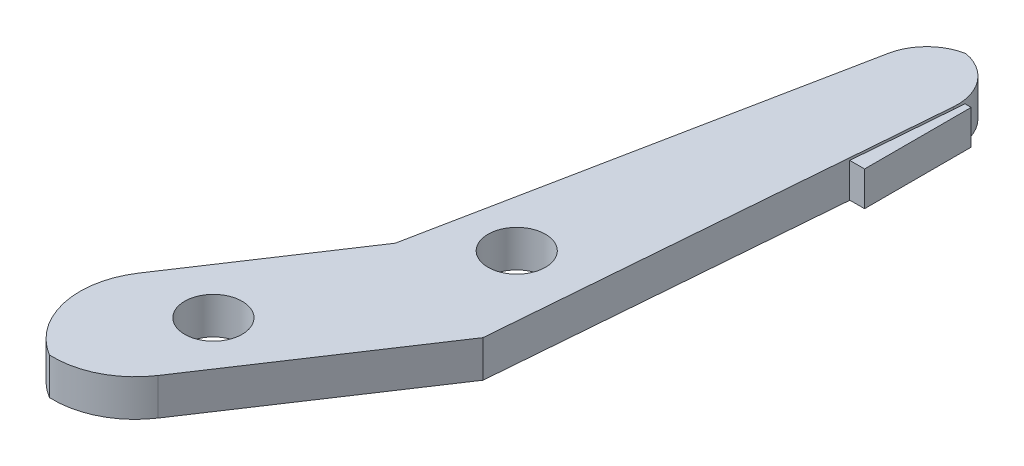
SolidWorks part; units mm, degrees
ref_plane "Front Plane" through (0, 0, 0) normal (0, 0, 1) x (1, 0, 0)
ref_plane "Top Plane" through (0, 0, 0) normal (0, 1, 0) x (1, 0, 0)
ref_plane "Right Plane" through (0, 0, 0) normal (1, 0, 0) x (0, 0, -1)
sketch "Sketch1" plane through (0, 0, 0) normal (0, 1, 0) x (1, 0, 0)
  line L0 (0, 0) -> (9.9579, 14.9947)
  line L1 (9.9579, 14.9947) -> (15.4442, 42.4519)
  line L6 (17.6176, 12.6862) -> (7.6597, -2.3085)
  line L7 (7.6597, -2.3085) -> (0, 0)
  line L9 (17.6176, 12.6862) -> (20.0339, 42.4519)
  line L10 (20.0339, 42.4519) -> (15.4442, 42.4519)
  point P2 (6.3021, 16.8607)
  point P6 (11.5877, 41.7741)
  point P7 (14.3875, 41.5565)
  point P10 (19.5325, 12.1091)
  point P11 (20.0339, 42.4519)
  dimension "D1" = 8
  dimension "D2" = 18
  dimension "D3" = 18
  dimension "D4" = 28
extrude "Boss-Extrude1" add sketch "Sketch1" along normal blind 2.25
fillet "Fillet1" radius 5 2 edges at (7.6597, 1.125, 2.3085) (0, 1.125, 0)
fillet "Fillet2" radius 3 2 edges at (15.4442, 1.125, -42.4519) (20.0339, 1.125, -42.4519)
sketch "Sketch2" plane through (0, 2.25, 0) normal (0, 1, 0) x (1, 0, 0)
  line L0 (17.6176, 12.6862) -> (19.7707, 39.2092) construction
  line L1 (9.7134, 0.7839) -> (17.6176, 12.6862) construction
  circle A0 centre (8.3533, 5.5145) radius 1.75
  circle A1 centre (14.06, 18.2987) radius 1.75
  point P4 (0, 0)
  point P5 (0, 0)
  dimension "D1" = 3.5
  dimension "D2" = 3.5
  dimension "D3" = 14
  dimension "D4" = 4
  dimension "D5" = 3.75
extrude "Cut-Extrude1" cut sketch "Sketch2" against normal through all
ref_plane "Plane1" through (20.2, 0, 0) normal (1, 0, 0) x (0, 0, -1)
sketch "Sketch4" plane through (20.2, -1.4847, -8.2019) normal (1, 0, 0) x (0, 0, -1)
  line L1 (31.6585, 3.5919) -> (25.1585, 3.5919)
  line L2 (31.6585, 3.5919) -> (31.6585, 1.4919)
  line L3 (31.6585, 1.4919) -> (25.1585, 1.4919)
  line L4 (25.1585, 3.5919) -> (25.1585, 1.4919)
  dimension "D1" = 2.1
  dimension "D2" = 6.5
extrude "Boss-Extrude2" add sketch "Sketch4" against normal up to surface (0.3765 mm away) up to face at (18.6941, 1.125, -25.9477)
extrude "Boss-Extrude3" add sketch "Sketch4<2>" against normal up to surface (0.3765 mm away) up to face at (19.1137, 1.0911, -31.1162)
sketch "Sketch4<2>" plane through (20.2, -1.4847, -8.2019) normal (1, 0, 0) x (0, 0, -1) same geometry as "Sketch4"
